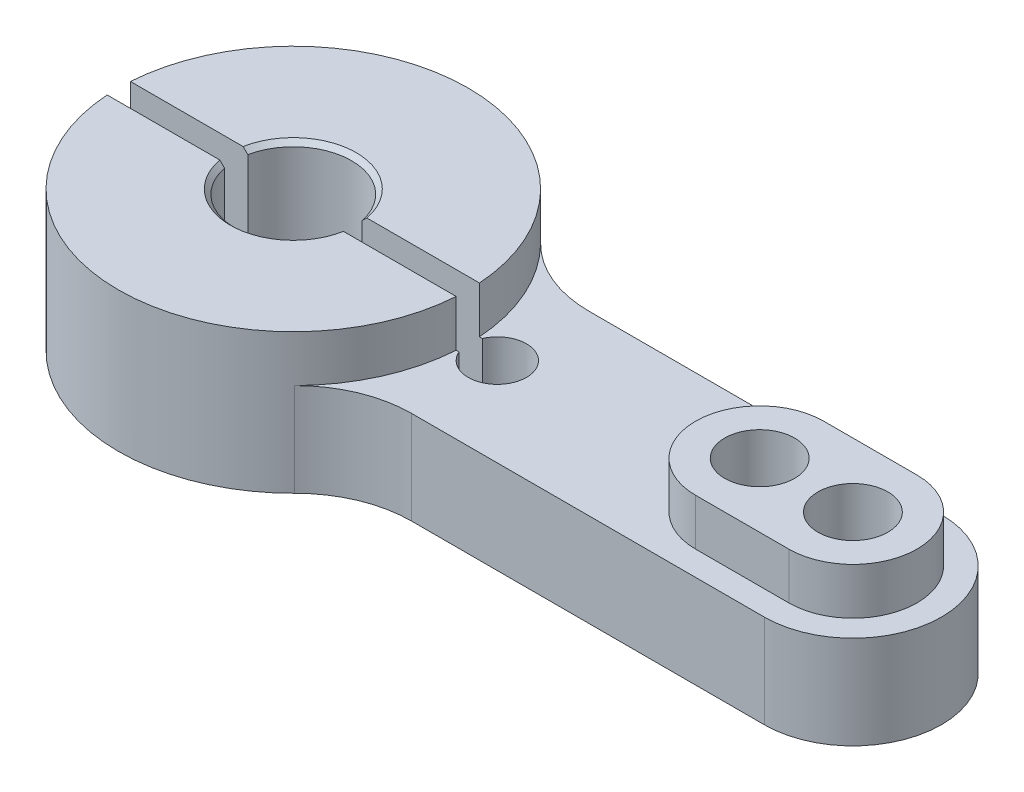
SolidWorks part; units mm, degrees
ref_plane "Front Plane" through (0, 0, 0) normal (0, 0, 1) x (1, 0, 0)
ref_plane "Top Plane" through (0, 0, 0) normal (0, 1, 0) x (1, 0, 0)
ref_plane "Right Plane" through (0, 0, 0) normal (1, 0, 0) x (0, 0, -1)
sketch "Sketch1" plane through (0, 0, 0) normal (0, 1, 0) x (1, 0, 0)
  line L5 (24, 3.8) -> (6.4661, 3.8)
  line L6 (24, -3.8) -> (6.4661, -3.8)
  circle A0 centre (0, 0) radius 7.5
  arc A1 (24, 3.8) -> (24, -3.8) centre (24, 0) cw
  circle A2 centre (8.75, 0) radius 1.25
  circle A3 centre (20, 0) radius 1.5
  circle A4 centre (24, 0) radius 1.5
  point P7 (27.8, 0)
  dimension "D1" = 8.75
  dimension "D3" = 15
  dimension "D8" = 3.8
  dimension "D2" = 11.25
  dimension "D4" = 4
  dimension "D5" = 3.8
  dimension "D6" = 3.8
  dimension "D7" = 7.6
  dimension "D9" = 3.8
extrude "Boss-Extrude2" add sketch "Sketch1" along normal blind 4
sketch "Sketch2" plane through (0, 4, 0) normal (0, 1, 0) x (1, 0, 0)
  circle A0 centre (0, 0) radius 7.5
extrude "Boss-Extrude3" add sketch "Sketch2" along normal blind 2
sketch "Sketch3" plane through (0, 4, 0) normal (0, 1, 0) x (1, 0, 0)
  line L1 (24, 2.75) -> (20, 2.75)
  line L3 (20, 0) -> (17.25, 0)
  line L4 (24, 0) -> (26.75, 0)
  line L5 (20, 2.75) -> (24, 2.75)
  line L6 (20, -2.75) -> (24, -2.75)
  arc A1 (24, -3.8) -> (24, 3.8) centre (24, 0) ccw construction
  arc A2 (20, -2.75) -> (20, 2.75) centre (20, 0) cw
  arc A3 (24, 2.75) -> (24, -2.75) centre (24, 0) cw
  circle A4 centre (20, 0) radius 1.5
  circle A5 centre (24, 0) radius 1.5
  dimension "D1" = 0
  dimension "D2" = 5.5
  dimension "D3" = 4
  dimension "D4" = 2.75
  dimension "D5" = 2.75
extrude "Boss-Extrude4" add sketch "Sketch3" along normal blind 2
sketch "Sketch4" plane through (0, 6, 0) normal (0, 1, 0) x (1, 0, 0)
  circle A0 centre (0, 0) radius 2.5
extrude "Cut-Extrude1" cut sketch "Sketch4" against normal blind 4
sketch "Sketch5" plane through (0, 0, 0) normal (0, -1, 0) x (-1, 0, 0)
  circle A0 centre (0, 0) radius 1
  dimension "D1" = 2
extrude "Cut-Extrude2" cut sketch "Sketch5" against normal through all
sketch "Sketch6" plane through (0, 0, 0) normal (0, -1, 0) x (-1, 0, 0)
  circle A0 centre (0, 0) radius 3.75
  dimension "D1" = 7.5
extrude "Cut-Extrude3" cut sketch "Sketch6" against normal blind 1
sketch "Sketch7" plane through (0, 0, 0) normal (0, -1, 0) x (-1, 0, 0)
  line L0 (-8.75, 0) -> (-8.75, -0.5)
  line L1 (-8.75, -0.5) -> (10.3852, -0.5)
  line L2 (10.3852, -0.5) -> (10.3852, 0.5)
  line L3 (10.3852, 0.5) -> (-8.75, 0.5)
  line L4 (-8.75, 0.5) -> (-8.75, 0)
  dimension "D1" = 0.5
  dimension "D2" = 1
extrude "Cut-Extrude4" cut sketch "Sketch7" against normal through all
fillet "Fillet2" radius 5 1 edges at (6.4661, 2, -3.8) type face fillet first side face at (1.9844, 3.3333, -3.6346) second side face at (15.233, 2, -3.8)
fillet "Fillet3" radius 5 1 edges at (6.4661, 2, 3.8) type face fillet first side face at (1.9844, 3.3333, 3.6346) second side face at (15.233, 2, 3.8)
chamfer "Chamfer1" distance 0.2 angle 45 2 edges at (0, 6, -2.5) (0, 6, 2.5)
